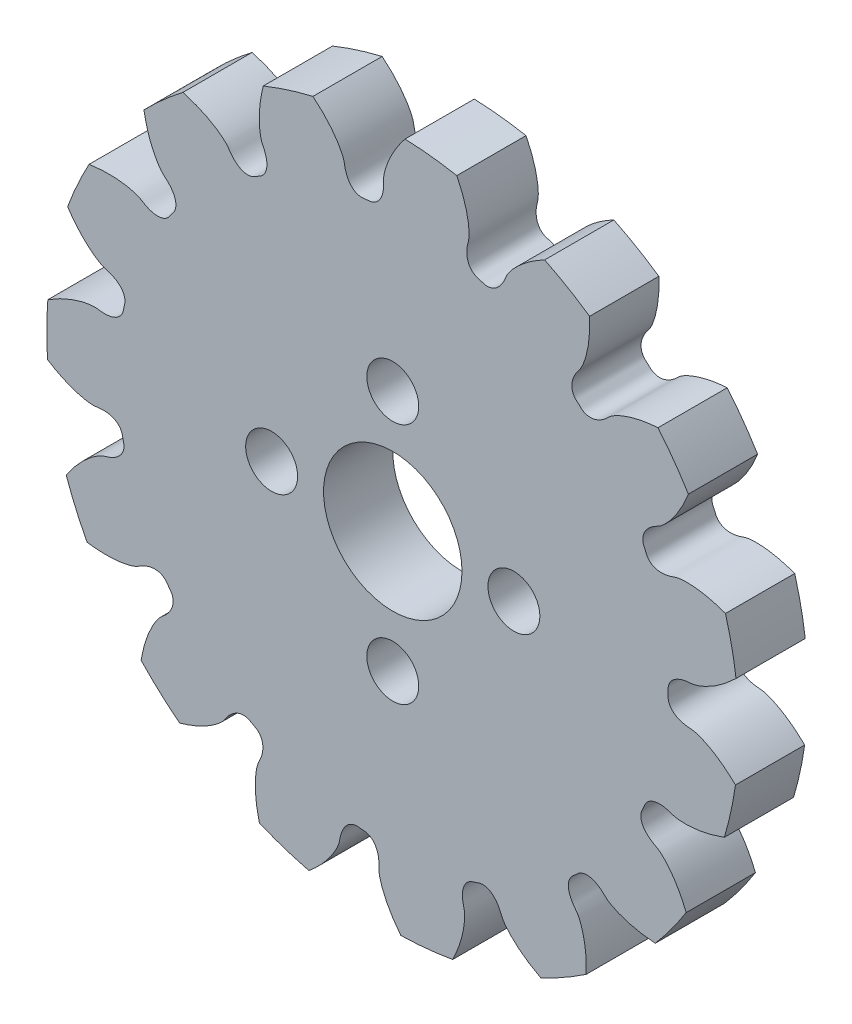
SolidWorks part; units mm, degrees
material "Д16 ГОСТ 4784-97"
ref_plane "FRONT" through (0, 0, 0) normal (0, 0, 1) x (1, 0, 0)
ref_plane "TOP" through (0, 0, 0) normal (0, 1, 0) x (1, 0, 0)
ref_plane "RIGHT" through (0, 0, 0) normal (1, 0, 0) x (0, 0, -1)
ref_axis "Ось1" through (0, 0, 50) along (0, 0, -1)
sketch "SketchRevolveSpurPinion" plane through (0, 0, 0) normal (1, 0, 0) x (0, 0, -1)
  line L0 (0, 0) -> (1, 0) construction
  line L1 (-5, 0) -> (-5, 20)
  line L2 (-5, 20) -> (-1, 20)
  line L3 (-1, 20) -> (-1, 0)
  line L4 (-1, 0) -> (-5, 0)
  dimension "D1" = 4
  dimension "D2" = 20
revolve "SpurPinion" add sketch "SketchRevolveSpurPinion" angle 360 about L0
sketch "SketchToothSpurPinion" plane through (0, 0, 0) normal (0, 0, 1) x (1, 0, 0)
  arc A0 (19.8423, 2.5595) -> (19.8423, -2.8298) centre (4.5858, -0.1352) cw
  spline S0 degree 3 poles (19.8423, -2.8298) (19.7062, -2.6961) (19.5011, -2.5072) (19.2226, -2.2767) (19.0258, -2.1249) (18.8361, -1.9888) (18.6544, -1.8675) (18.4815, -1.7605) (18.3181, -1.667) (18.1648, -1.5862) (18.0225, -1.5172) (17.8917, -1.4592) (17.7729, -1.4114) (17.6667, -1.3729) (17.5736, -1.3425) (17.4939, -1.3198) (17.3243, -1.2755) (17.1585, -1.2774) (17.0031, -1.2568) (16.9561, -1.2499) (16.9098, -1.242) (16.8644, -1.2333) (16.8197, -1.2238) (16.7757, -1.2134) (16.7325, -1.2022) (16.69, -1.19) (16.6483, -1.1769) (16.6072, -1.1629) (16.5668, -1.1479) (16.527, -1.132) (16.488, -1.1149) (16.4495, -1.0968) (16.4117, -1.0775) (16.3746, -1.0569) (16.338, -1.035) (16.3021, -1.0117) (16.2669, -0.9869) (16.2323, -0.9604) (16.1985, -0.9322) (16.1655, -0.902) (16.1335, -0.8698) (16.1025, -0.8353) (16.0727, -0.7985) (16.0444, -0.7593) (16.0177, -0.7175) (15.9932, -0.6731) (15.971, -0.626) (15.9516, -0.5765) (15.9354, -0.5247) (15.9228, -0.4708) (15.9141, -0.4154) (15.9101, -0.3639) (15.9085, -0.2703) (15.9128, -0.1352) (15.9085, 0) (15.9101, 0.0936) (15.9141, 0.1451) (15.9228, 0.2005) (15.9354, 0.2544) (15.9516, 0.3062) (15.971, 0.3557) (15.9932, 0.4027) (16.0177, 0.4472) (16.0444, 0.489) (16.0727, 0.5282) (16.1025, 0.565) (16.1335, 0.5995) (16.1655, 0.6317) (16.1985, 0.6619) (16.2323, 0.6901) (16.2669, 0.7166) (16.3021, 0.7414) (16.338, 0.7647) (16.3746, 0.7866) (16.4117, 0.8072) (16.4495, 0.8265) (16.488, 0.8446) (16.527, 0.8617) (16.5668, 0.8776) (16.6072, 0.8926) (16.6483, 0.9066) (16.69, 0.9197) (16.7325, 0.9318) (16.7757, 0.9431) (16.8197, 0.9535) (16.8644, 0.963) (16.9098, 0.9717) (16.9561, 0.9796) (17.0031, 0.9865) (17.1585, 1.007) (17.3243, 1.0052) (17.4939, 1.0495) (17.5736, 1.0722) (17.6667, 1.1026) (17.7729, 1.1411) (17.8917, 1.1889) (18.0225, 1.2469) (18.1648, 1.3159) (18.3181, 1.3967) (18.4815, 1.4902) (18.6544, 1.5972) (18.8361, 1.7185) (19.0258, 1.8546) (19.2226, 2.0064) (19.5011, 2.2369) (19.7062, 2.4258) (19.8423, 2.5595) knots 0 0 0 0 0.056361 0.082316 0.106788 0.129777 0.151283 0.171306 0.189846 0.206902 0.222476 0.236566 0.249173 0.260297 0.269937 0.278095 0.284769 0.321669 0.326412 0.33109 0.335705 0.340261 0.34476 0.349206 0.353603 0.357953 0.362262 0.366534 0.370775 0.37499 0.379185 0.383368 0.387544 0.391724 0.395914 0.400124 0.404365 0.408647 0.41298 0.417377 0.421849 0.426407 0.431063 0.435825 0.440701 0.445696 0.450813 0.456049 0.461396 0.466842 0.472369 0.477956 0.4821 0.5 0.5179 0.522044 0.527631 0.533158 0.538604 0.543951 0.549187 0.554304 0.559299 0.564175 0.568937 0.573593 0.578151 0.582623 0.58702 0.591353 0.595635 0.599876 0.604086 0.608276 0.612456 0.616632 0.620815 0.62501 0.629225 0.633466 0.637738 0.642047 0.646397 0.650794 0.65524 0.659739 0.664295 0.66891 0.673588 0.678331 0.715231 0.721905 0.730063 0.739703 0.750827 0.763434 0.777524 0.793098 0.810154 0.828694 0.848717 0.870223 0.893212 0.917684 0.943639 1 1 1 1
  point P108 (11.3503, -0.3897)
extrude "ToothExtrudeCutSpurPinion" cut sketch "SketchToothSpurPinion" against normal blind 5 and the other way blind 5
sketch "AuxiliarySketchSpurPinion" plane through (0, 0, 0) normal (0, 0, 1) x (1, 0, 0)
  circle A0 centre (0, 0) radius 13.59 construction
  circle A1 centre (0, 0) radius 12.7704 construction
  circle A2 centre (0, 0) radius 12.8041 construction
  circle A3 centre (0, 0) radius 15.402 construction
  circle A4 centre (0, 0) radius 11.325 construction
  dimension "PitchDiameter" = 27.18
  dimension "BaseDiameter" = 25.5408
  dimension "FormDiameter" = 25.6083
  dimension "MajorDiameter" = 30.804
  dimension "MinorDiameter" = 22.65
sketch "Эскиз6" plane through (0, 0, 5) normal (0, 0, 1) x (1, 0, 0)
  circle A0 centre (0, 0) radius 7 construction
  circle A1 centre (0, 0) radius 8.5 construction
  circle A3 centre (0, 7) radius 1.5
  circle A4 centre (7, 0) radius 1.5
  circle A5 centre (0, -7) radius 1.5
  circle A6 centre (-7, 0) radius 1.5
  circle A7 centre (0, 0) radius 4
  dimension "D1" = 14
  dimension "D2" = 17
  dimension "D3" = 8
extrude "Вырез-Вытянуть3" cut sketch "Эскиз6" against normal through all
pattern_circular "Круговой массив1" count 15 over 360 about axis through (0, 0, 5) along (0, 0, 1) of "ToothExtrudeCutSpurPinion"
